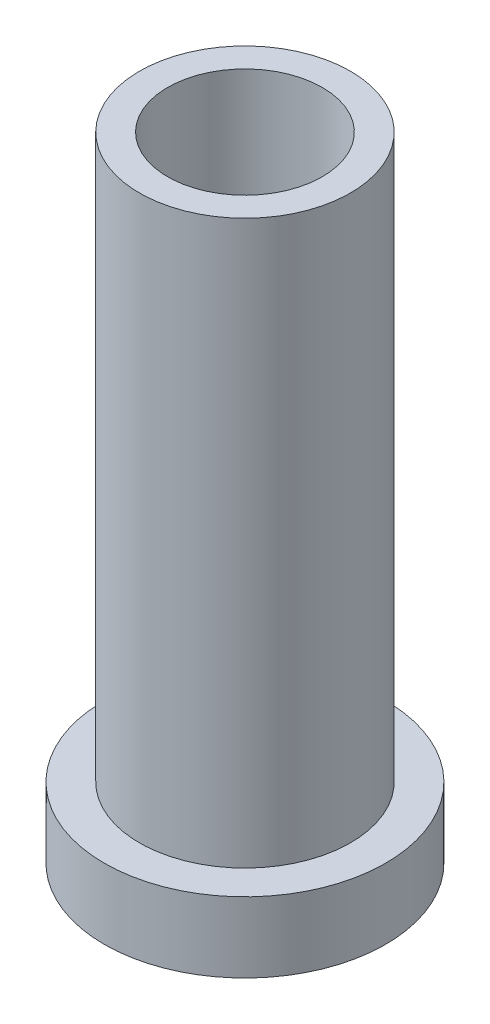
SolidWorks part; units mm, degrees
ref_plane "Front Plane" through (0, 0, 0) normal (0, 0, 1) x (1, 0, 0)
ref_plane "Top Plane" through (0, 0, 0) normal (0, 1, 0) x (1, 0, 0)
ref_plane "Right Plane" through (0, 0, 0) normal (1, 0, 0) x (0, 0, -1)
sketch "Sketch1" plane through (0, 0, 0) normal (0, 1, 0) x (1, 0, 0)
  circle A0 centre (0, 0) radius 10
  circle A1 centre (0, 0) radius 5.5
  circle A2 centre (0, 0) radius 7.5
  dimension "D1" = 20
  dimension "D2" = 15
  dimension "D3" = 11
extrude "Boss-Extrude1" add sketch "Sketch1" along normal blind 5 contours A0
extrude "Boss-Extrude2" add sketch "Sketch1<3>" along normal blind 45 contours A2
sketch "Sketch1<3>" plane through (0, 0, 0) normal (0, 1, 0) x (1, 0, 0) same geometry as "Sketch1"
extrude "Cut-Extrude1" cut sketch "Sketch1<4>" along normal through all contours A1
sketch "Sketch1<4>" plane through (0, 0, 0) normal (0, 1, 0) x (1, 0, 0) same geometry as "Sketch1"
